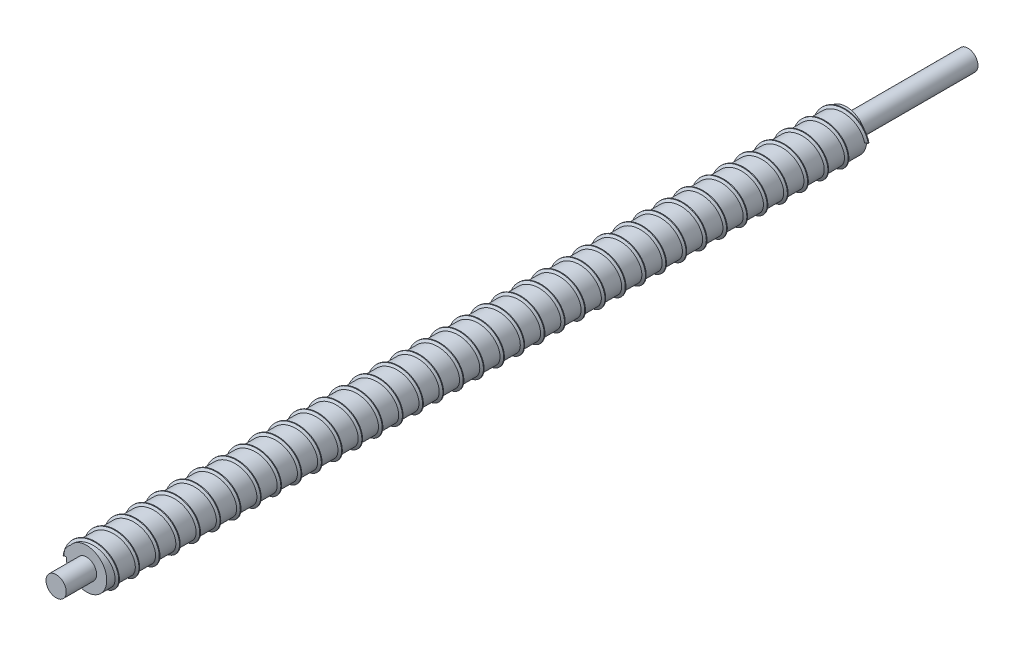
SolidWorks part; units mm, degrees
ref_plane "Front Plane" through (0, 0, 0) normal (0, 0, 1) x (1, 0, 0)
ref_plane "Top Plane" through (0, 0, 0) normal (0, 1, 0) x (1, 0, 0)
ref_plane "Right Plane" through (0, 0, 0) normal (1, 0, 0) x (0, 0, -1)
sketch "Sketch1" plane through (0, 0, 0) normal (0, 0, 1) x (1, 0, 0)
  circle A0 centre (0, 0) radius 10
  dimension "D1" = 20
extrude "Boss-Extrude1" add sketch "Sketch1" along normal blind 450
sketch "Sketch2" plane through (0, 0, 450) normal (0, 0, 1) x (1, 0, 0)
  circle A0 centre (0, 0) radius 10
  circle A1 centre (0, 0) radius 5
  dimension "D1" = 10
extrude "Cut-Extrude1" cut sketch "Sketch2" against normal blind 15
sketch "Sketch3" plane through (0, 0, 0) normal (0, 0, -1) x (-1, 0, 0)
  circle A0 centre (0, 0) radius 10
  circle A1 centre (0, 0) radius 5
  dimension "D1" = 10
extrude "Cut-Extrude2" cut sketch "Sketch3" against normal blind 60
sketch "Sketch6" plane through (0, 0, 435) normal (0, 0, 1) x (1, 0, 0)
  circle A0 centre (0, 0) radius 10
curve "Helix/Spiral2" pitch 10 height 375 turns 37.5
sketch "Sketch8" plane through (0, 0, 0) normal (0, 1, 0) x (1, 0, 0)
  line L0 (9.1074, -60) -> (11.1487, -60)
  line L2 (9.1074, -60) -> (9.1074, -61.546)
  line L3 (9.1074, -61.546) -> (11.1487, -60.3675)
  line L4 (11.1487, -60) -> (11.1487, -60.3675)
  line L6 (11.7851, -60) -> (9.1074, -58.454) [skipped]
  arc A0 (9.1074, -60) -> (10.8926, -60) centre (10, -60) ccw construction
sweep "Sweep2" add profiles "Sketch8" path "Helix/Spiral2"
sketch "Sketch9" plane through (0, 0, 435) normal (0, 0, 1) x (1, 0, 0)
  circle A0 centre (0, 0) radius 5
  circle A1 centre (0, 0) radius 11.1131
extrude "Cut-Extrude3" cut sketch "Sketch9" along normal blind 10
